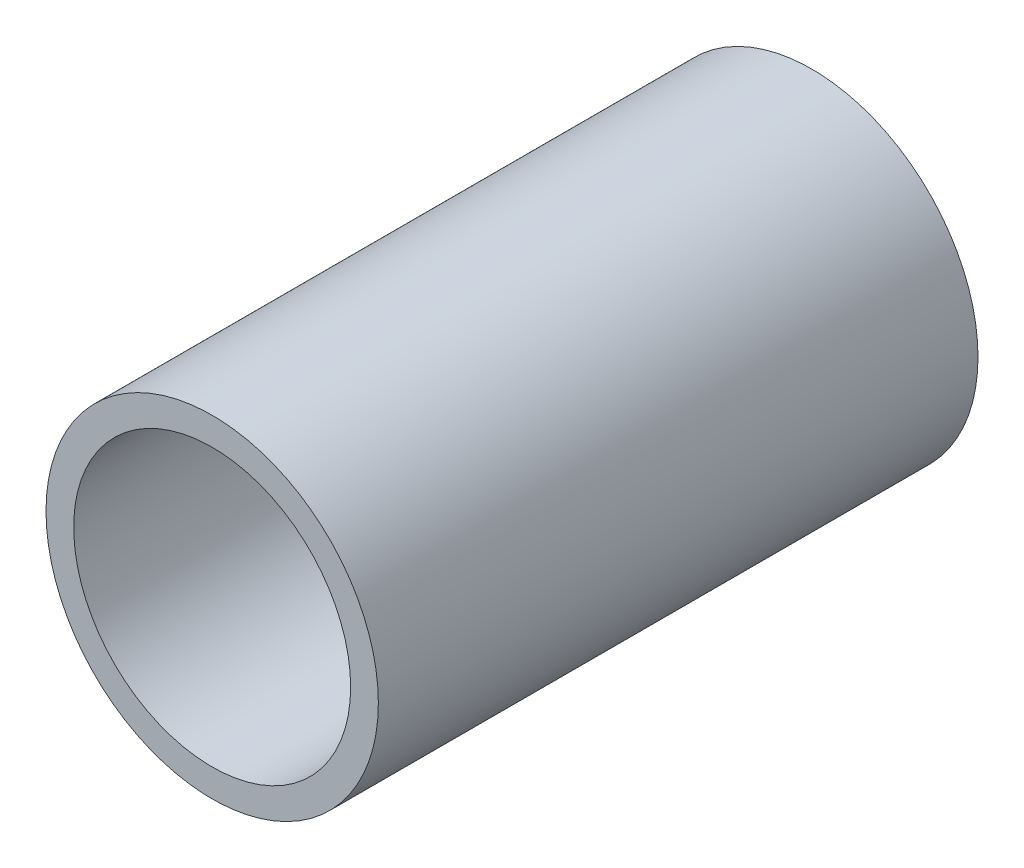
SolidWorks part; units mm, degrees
material "PLA 50%"
ref_plane "Front Plane" through (0, 0, 0) normal (0, 0, 1) x (1, 0, 0)
ref_plane "Top Plane" through (0, 0, 0) normal (0, 1, 0) x (1, 0, 0)
ref_plane "Right Plane" through (0, 0, 0) normal (1, 0, 0) x (0, 0, -1)
ref_axis "X" through (-88.99, 0, 0) along (1, 0, 0)
ref_axis "Y" through (0, 55, 0) along (0, -1, 0)
ref_axis "Z" through (0, 0, -88.99) along (0, 0, 1)
sketch "Sketch1" plane through (0, 0, 0) normal (0, 0, 1) x (1, 0, 0)
  circle A0 centre (0, 0) radius 5
  circle A1 centre (0, 0) radius 6
  dimension "D1" = 10
  dimension "D2" = 12
extrude "Boss-Extrude1" add sketch "Sketch1" along normal up to surface (21.6512 mm away)
